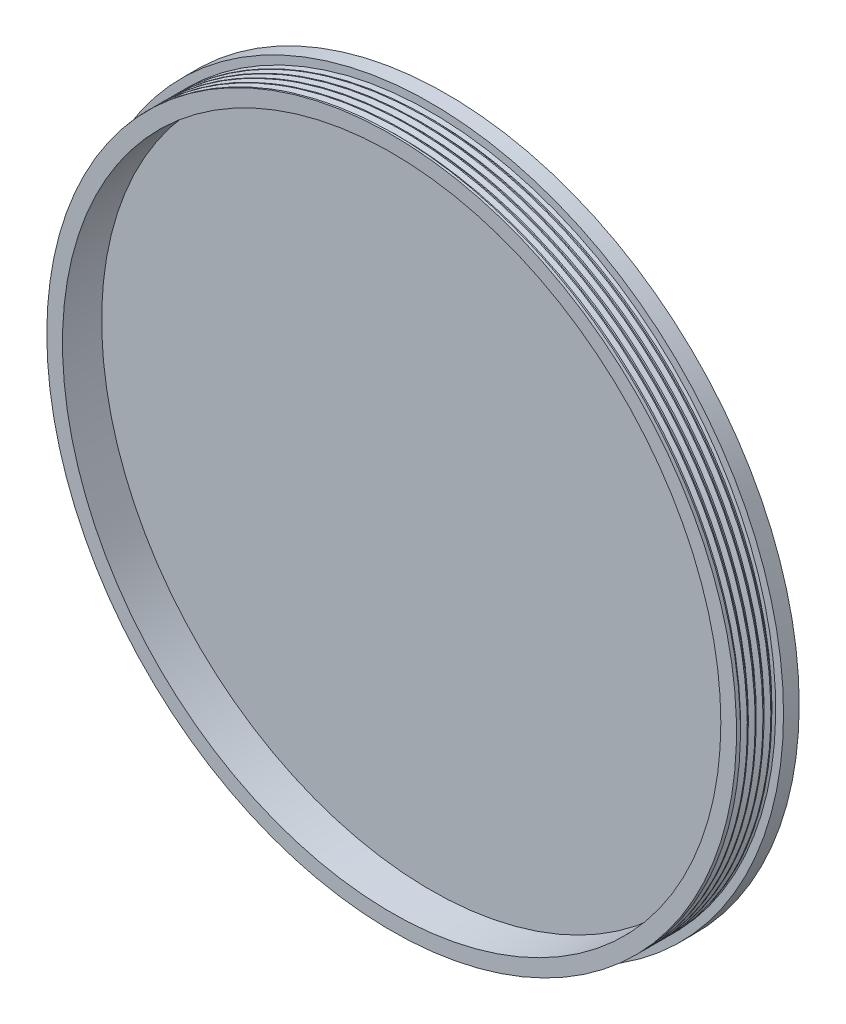
SolidWorks part; units mm, degrees
ref_plane "Спереди" through (0, 0, 0) normal (0, 0, 1) x (1, 0, 0)
ref_plane "Сверху" through (0, 0, 0) normal (0, 1, 0) x (1, 0, 0)
ref_plane "Справа" through (0, 0, 0) normal (1, 0, 0) x (0, 0, -1)
sketch "Эскиз1" plane through (0, 0, 0) normal (0, 0, 1) x (1, 0, 0)
  circle A0 centre (0, 0) radius 45
extrude "Бобышка-Вытянуть1" add sketch "Эскиз1" along normal blind 2
ref_plane "Плоскость4" through (0, 0, 2) normal (0, 0, 1) x (1, 0, 0)
ref_plane "Плоскость5" through (0, 0, 2) normal (0, 0, 1) x (1, 0, 0)
sketch "Эскиз2" plane through (0, 0, 2) normal (0, 0, 1) x (1, 0, 0)
  circle A0 centre (0, 0) radius 44
extrude "Бобышка-Вытянуть2" add sketch "Эскиз2" along normal blind 5 contours A0
thread "Резьба1" pitch 1 method cut profile "Профиль резьбы1" start angle 0, offset 0, length 5, pitch 1, diameter 88
ref_plane "Плоскость6" through (-44, 0, 7) normal (0, -1, 0) x (-1, 0, 0)
sketch "Профиль резьбы1" plane through (-44, 0, 7) normal (0, -1, 0) x (-1, 0, 0)
  line L0 (0, 0) -> (0, 1) construction
  line L11 (0, 0) -> (0, 0.875)
  line L12 (0, 0.875) -> (-0.5413, 0.5625)
  line L13 (-0.5413, 0.5625) -> (-0.5413, 0.3125)
  line L15 (-0.5413, 0.3125) -> (0, 0)
  line L17 (-0.5413, 0.4375) -> (0, 0.4375) construction
  point P2 (0, 0)
  dimension "Pitch" = 1
  dimension "Profile_Angle" = 60
  dimension "Profile_Land" = 0.25
  dimension "Profile_Height" = 0.5413
ref_plane "Плоскость7" through (0, 0, 7) normal (0, 0, 1) x (1, 0, 0)
sketch "Эскиз5" plane through (0, 0, 7) normal (0, 0, 1) x (1, 0, 0)
  circle A0 centre (0, 0) radius 42
extrude "Вырез-Вытянуть1" cut sketch "Эскиз5" against normal blind 5 contours A0
sketch "Эскиз6" plane through (0, 0, 2) normal (0, 0, 1) x (1, 0, 0)
  line L1 (-42, 0) -> (42, 0) construction
  circle A0 centre (0, 0) radius 42 construction
